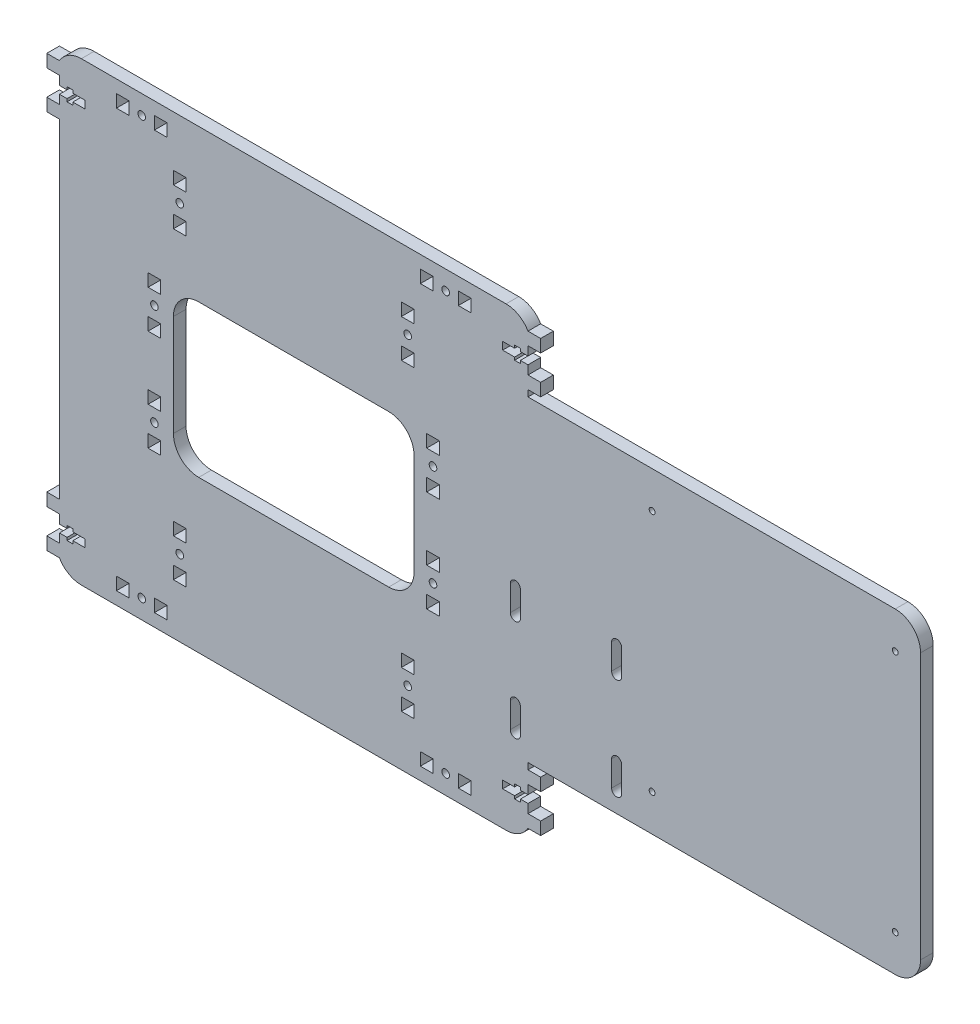
SolidWorks part; units mm, degrees
ref_plane "Front Plane" through (0, 0, 0) normal (0, 0, 1) x (1, 0, 0)
ref_plane "Top Plane" through (0, 0, 0) normal (0, 1, 0) x (1, 0, 0)
ref_plane "Right Plane" through (0, 0, 0) normal (1, 0, 0) x (0, 0, -1)
sketch "Sketch1" plane through (0, 0, 0) normal (0, 0, 1) x (1, 0, 0)
  line L0 (0, 0) -> (264.3375, 0) construction
  line L1 (-92.5, 90) -> (92.5, 90)
  line L2 (-92.5, 90) -> (-92.5, -90) construction
  line L3 (-92.5, -90) -> (92.5, -90)
  line L4 (92.5, 90) -> (92.5, -90) construction
  line L5 (0, 0) -> (0, 175.0626) construction
  line L6 (-92.5, 82.5) -> (92.5, 82.5) construction
  line L7 (92.5, -82.5) -> (-92.5, -82.5) construction
  line L8 (-92.5, 75) -> (-91.2792, 75) construction
  line L9 (-92.5, 76.5) -> (-92.5, 80)
  line L10 (-97.5, 80) -> (-97.5, 85)
  line L11 (-97.5, 85) -> (-92.5, 85)
  line L12 (-97.5, 80) -> (-92.5, 80)
  line L13 (-92.5, 73.5) -> (-92.5, 70)
  line L14 (-92.5, 70) -> (-97.5, 70)
  line L15 (-97.5, 70) -> (-97.5, 65)
  line L16 (-97.5, 65) -> (-92.5, 65)
  line L17 (-92.5, 76.5) -> (-92.5, 73.5) construction
  line L18 (-92.5, 73.5) -> (-89.5, 73.5)
  line L19 (-87.2, 73.5) -> (-87.2, 72.4)
  line L20 (-89.5, 77.6) -> (-87.2, 77.6)
  line L21 (-89.5, 72.4) -> (-89.5, 73.5)
  line L22 (-87.2, 73.5) -> (-82.5, 73.5)
  line L23 (-82.5, 73.5) -> (-82.5, 76.5)
  line L24 (-82.5, 76.5) -> (-87.2, 76.5)
  line L25 (-89.5, 76.5) -> (-89.5, 77.6)
  line L26 (-87.2, 72.4) -> (-89.5, 72.4)
  line L27 (-87.2, 77.6) -> (-87.2, 76.5)
  line L28 (-89.5, 76.5) -> (-92.5, 76.5)
  line L29 (-82.5, 75) -> (-92.5, 75) construction
  line L30 (-97.5, -85) -> (-92.5, -85)
  line L31 (-97.5, -80) -> (-97.5, -85)
  line L32 (-97.5, -80) -> (-92.5, -80)
  line L33 (-92.5, -76.5) -> (-92.5, -80)
  line L34 (-89.5, -76.5) -> (-92.5, -76.5)
  line L35 (-89.5, -76.5) -> (-89.5, -77.6)
  line L36 (-89.5, -77.6) -> (-87.2, -77.6)
  line L37 (-87.2, -77.6) -> (-87.2, -76.5)
  line L38 (-82.5, -76.5) -> (-87.2, -76.5)
  line L39 (-82.5, -73.5) -> (-82.5, -76.5)
  line L40 (-87.2, -73.5) -> (-82.5, -73.5)
  line L41 (-87.2, -73.5) -> (-87.2, -72.4)
  line L42 (-87.2, -72.4) -> (-89.5, -72.4)
  line L43 (-89.5, -72.4) -> (-89.5, -73.5)
  line L44 (-92.5, -73.5) -> (-89.5, -73.5)
  line L45 (-92.5, -73.5) -> (-92.5, -70)
  line L46 (-92.5, -70) -> (-97.5, -70)
  line L47 (-97.5, -70) -> (-97.5, -65)
  line L48 (-97.5, -65) -> (-92.5, -65)
  line L49 (82.5, 75) -> (92.5, 75) construction
  line L50 (92.5, 76.5) -> (92.5, 73.5) construction
  line L51 (92.5, 75) -> (91.2792, 75) construction
  line L52 (97.5, -65) -> (92.5, -65)
  line L53 (97.5, -70) -> (97.5, -65)
  line L54 (92.5, -70) -> (97.5, -70)
  line L55 (92.5, -73.5) -> (92.5, -70)
  line L56 (92.5, -73.5) -> (89.5, -73.5)
  line L57 (89.5, -72.4) -> (89.5, -73.5)
  line L58 (87.2, -72.4) -> (89.5, -72.4)
  line L59 (87.2, -73.5) -> (87.2, -72.4)
  line L60 (87.2, -73.5) -> (82.5, -73.5)
  line L61 (82.5, -73.5) -> (82.5, -76.5)
  line L62 (82.5, -76.5) -> (87.2, -76.5)
  line L63 (87.2, -77.6) -> (87.2, -76.5)
  line L64 (89.5, -77.6) -> (87.2, -77.6)
  line L65 (89.5, -76.5) -> (89.5, -77.6)
  line L66 (89.5, -76.5) -> (92.5, -76.5)
  line L67 (92.5, -76.5) -> (92.5, -80)
  line L68 (97.5, -80) -> (92.5, -80)
  line L69 (97.5, -80) -> (97.5, -85)
  line L70 (97.5, -85) -> (92.5, -85)
  line L71 (89.5, 76.5) -> (92.5, 76.5)
  line L72 (87.2, 77.6) -> (87.2, 76.5)
  line L73 (87.2, 72.4) -> (89.5, 72.4)
  line L74 (89.5, 76.5) -> (89.5, 77.6)
  line L75 (82.5, 76.5) -> (87.2, 76.5)
  line L76 (82.5, 73.5) -> (82.5, 76.5)
  line L77 (87.2, 73.5) -> (82.5, 73.5)
  line L78 (89.5, 72.4) -> (89.5, 73.5)
  line L79 (89.5, 77.6) -> (87.2, 77.6)
  line L80 (87.2, 73.5) -> (87.2, 72.4)
  line L81 (92.5, 73.5) -> (89.5, 73.5)
  line L82 (97.5, 65) -> (92.5, 65)
  line L83 (97.5, 70) -> (97.5, 65)
  line L84 (92.5, 70) -> (97.5, 70)
  line L85 (92.5, 73.5) -> (92.5, 70)
  line L86 (97.5, 80) -> (92.5, 80)
  line L87 (97.5, 85) -> (92.5, 85)
  line L88 (97.5, 80) -> (97.5, 85)
  line L89 (92.5, 76.5) -> (92.5, 80)
  line L90 (92.5, 90) -> (92.5, 85)
  line L91 (92.5, 65) -> (92.5, -65) construction
  line L92 (92.5, -85) -> (92.5, -90)
  line L93 (-92.5, -85) -> (-92.5, -90)
  line L94 (-92.5, 65) -> (-92.5, -65) construction
  line L95 (-92.5, 90) -> (-92.5, 85)
  line L96 (92.5, 65) -> (92.5, 62.5)
  line L97 (-47.5, 30) -> (47.5, 30)
  line L98 (-47.5, 30) -> (-47.5, -30)
  line L99 (-47.5, -30) -> (47.5, -30)
  line L100 (47.5, 30) -> (47.5, -30)
  line L101 (92.5, 62.5) -> (247.5, 62.5)
  line L102 (247.5, 62.5) -> (247.5, -62.5)
  line L103 (247.5, -62.5) -> (92.5, -62.5)
  line L104 (92.5, -62.5) -> (92.5, -65)
  line L105 (127.5, -49.75) -> (73.57, -49.75) construction
  line L106 (127.5, -9.75) -> (73.57, -9.75) construction
  line L107 (127.5, -9.75) -> (127.5, -49.75) construction
  line L108 (127.5, -14.75) -> (127.5, -4.75) construction
  line L109 (125.5, -14.75) -> (125.5, -4.75)
  line L110 (129.5, -14.75) -> (129.5, -4.75)
  line L111 (87.5, -14.75) -> (87.5, -4.75) construction
  line L112 (85.5, -14.75) -> (85.5, -4.75)
  line L113 (89.5, -14.75) -> (89.5, -4.75)
  line L114 (87.5, -54.75) -> (87.5, -44.75) construction
  line L115 (85.5, -54.75) -> (85.5, -44.75)
  line L116 (89.5, -54.75) -> (89.5, -44.75)
  line L117 (127.5, -54.75) -> (127.5, -44.75) construction
  line L118 (125.5, -54.75) -> (125.5, -44.75)
  line L119 (129.5, -54.75) -> (129.5, -44.75)
  line L120 (-92.5, 65) -> (-92.5, -65)
  line L126 (141.5, 48) -> (237.5, 48) construction
  line L127 (141.5, 48) -> (141.5, -48) construction
  line L128 (141.5, -48) -> (237.5, -48) construction
  line L129 (237.5, 48) -> (237.5, -48) construction
  arc A4 (125.5, -14.75) -> (129.5, -14.75) centre (127.5, -14.75) ccw
  arc A5 (129.5, -4.75) -> (125.5, -4.75) centre (127.5, -4.75) ccw
  arc A6 (85.5, -14.75) -> (89.5, -14.75) centre (87.5, -14.75) ccw
  arc A7 (89.5, -4.75) -> (85.5, -4.75) centre (87.5, -4.75) ccw
  arc A8 (85.5, -54.75) -> (89.5, -54.75) centre (87.5, -54.75) ccw
  arc A9 (89.5, -44.75) -> (85.5, -44.75) centre (87.5, -44.75) ccw
  arc A10 (125.5, -54.75) -> (129.5, -54.75) centre (127.5, -54.75) ccw
  arc A11 (129.5, -44.75) -> (125.5, -44.75) centre (127.5, -44.75) ccw
  circle A12 centre (141.5, 48) radius 1.15
  circle A13 centre (237.5, 48) radius 1.15
  circle A14 centre (237.5, -48) radius 1.15
  circle A15 centre (141.5, -48) radius 1.15
  point P113 (127.5, -9.75)
  point P118 (0, 0)
  point P119 (41.7626, 62.5)
  point P122 (87.5, -9.75)
  point P129 (87.5, -49.75)
  point P136 (127.5, -49.75)
  point P141 (0, 0)
  line B0 (-65, 82.5) -> (-55, 82.5) construction
  line B1 (-65, 85) -> (-70, 85)
  line B2 (-65, 85) -> (-65, 80)
  line B3 (-65, 80) -> (-70, 80)
  line B4 (-70, 85) -> (-70, 80)
  line B5 (-55, 85) -> (-50, 85)
  line B6 (-55, 85) -> (-55, 80)
  line B7 (-55, 80) -> (-50, 80)
  line B8 (-50, 85) -> (-50, 80)
  line B9 (-60, 82.5) -> (-60, 89.4724) construction
  circle B10 centre (-60, 82.5) radius 1.5
  line B11 (65, 85) -> (70, 85)
  line B12 (65, 85) -> (65, 80)
  line B13 (65, 80) -> (70, 80)
  line B14 (70, 85) -> (70, 80)
  line B15 (55, 85) -> (50, 85)
  line B16 (55, 85) -> (55, 80)
  line B17 (55, 80) -> (50, 80)
  line B18 (50, 85) -> (50, 80)
  circle B19 centre (60, 82.5) radius 1.5
  line B20 (65, -85) -> (70, -85)
  line B21 (65, -85) -> (65, -80)
  line B22 (65, -80) -> (70, -80)
  line B23 (70, -85) -> (70, -80)
  line B24 (55, -85) -> (50, -85)
  line B25 (55, -85) -> (55, -80)
  line B26 (55, -80) -> (50, -80)
  line B27 (50, -85) -> (50, -80)
  circle B28 centre (60, -82.5) radius 1.5
  line B29 (-65, -85) -> (-70, -85)
  line B30 (-65, -85) -> (-65, -80)
  line B31 (-65, -80) -> (-70, -80)
  line B32 (-70, -85) -> (-70, -80)
  line B33 (-55, -85) -> (-50, -85)
  line B34 (-55, -85) -> (-55, -80)
  line B35 (-55, -80) -> (-50, -80)
  line B36 (-50, -85) -> (-50, -80)
  circle B37 centre (-60, -82.5) radius 1.5
  line B38 (55, 25) -> (55, 15) construction
  line B39 (57.5, 25) -> (57.5, 30)
  line B40 (57.5, 25) -> (52.5, 25)
  line B41 (52.5, 25) -> (52.5, 30)
  line B42 (57.5, 30) -> (52.5, 30)
  line B43 (57.5, 15) -> (57.5, 10)
  line B44 (57.5, 15) -> (52.5, 15)
  line B45 (52.5, 15) -> (52.5, 10)
  line B46 (57.5, 10) -> (52.5, 10)
  line B47 (55, 20) -> (61.9724, 20) construction
  circle B48 centre (55, 20) radius 1.5
  line B49 (-57.5, 25) -> (-57.5, 30)
  line B50 (-57.5, 25) -> (-52.5, 25)
  line B51 (-52.5, 25) -> (-52.5, 30)
  line B52 (-57.5, 30) -> (-52.5, 30)
  line B53 (-57.5, 15) -> (-57.5, 10)
  line B54 (-57.5, 15) -> (-52.5, 15)
  line B55 (-52.5, 15) -> (-52.5, 10)
  line B56 (-57.5, 10) -> (-52.5, 10)
  line B57 (-55, 20) -> (-61.9724, 20) construction
  circle B58 centre (-55, 20) radius 1.5
  line B59 (57.5, -25) -> (57.5, -30)
  line B60 (57.5, -25) -> (52.5, -25)
  line B61 (52.5, -25) -> (52.5, -30)
  line B62 (57.5, -30) -> (52.5, -30)
  line B63 (57.5, -15) -> (57.5, -10)
  line B64 (57.5, -15) -> (52.5, -15)
  line B65 (52.5, -15) -> (52.5, -10)
  line B66 (57.5, -10) -> (52.5, -10)
  circle B67 centre (55, -20) radius 1.5
  line B68 (-57.5, -25) -> (-57.5, -30)
  line B69 (-57.5, -25) -> (-52.5, -25)
  line B70 (-52.5, -25) -> (-52.5, -30)
  line B71 (-57.5, -30) -> (-52.5, -30)
  line B72 (-57.5, -15) -> (-57.5, -10)
  line B73 (-57.5, -15) -> (-52.5, -15)
  line B74 (-52.5, -15) -> (-52.5, -10)
  line B75 (-57.5, -10) -> (-52.5, -10)
  line B76 (-55, -20) -> (-61.9724, -20) construction
  circle B77 centre (-55, -20) radius 1.5
  line B78 (47.5, 65) -> (47.5, 70)
  line B79 (47.5, 65) -> (42.5, 65)
  line B80 (42.5, 65) -> (42.5, 70)
  line B81 (47.5, 70) -> (42.5, 70)
  line B82 (47.5, 55) -> (47.5, 50)
  line B83 (47.5, 55) -> (42.5, 55)
  line B84 (42.5, 55) -> (42.5, 50)
  line B85 (47.5, 50) -> (42.5, 50)
  circle B86 centre (45, 60) radius 1.5
  line B87 (-47.5, 65) -> (-47.5, 70)
  line B88 (-47.5, 65) -> (-42.5, 65)
  line B89 (-42.5, 65) -> (-42.5, 70)
  line B90 (-47.5, 70) -> (-42.5, 70)
  line B91 (-47.5, 55) -> (-47.5, 50)
  line B92 (-47.5, 55) -> (-42.5, 55)
  line B93 (-42.5, 55) -> (-42.5, 50)
  line B94 (-47.5, 50) -> (-42.5, 50)
  circle B95 centre (-45, 60) radius 1.5
  line B96 (47.5, -65) -> (47.5, -70)
  line B97 (47.5, -65) -> (42.5, -65)
  line B98 (42.5, -65) -> (42.5, -70)
  line B99 (47.5, -70) -> (42.5, -70)
  line B100 (47.5, -55) -> (47.5, -50)
  line B101 (47.5, -55) -> (42.5, -55)
  line B102 (42.5, -55) -> (42.5, -50)
  line B103 (47.5, -50) -> (42.5, -50)
  circle B104 centre (45, -60) radius 1.5
  line B105 (-47.5, -65) -> (-47.5, -70)
  line B106 (-47.5, -65) -> (-42.5, -65)
  line B107 (-42.5, -65) -> (-42.5, -70)
  line B108 (-47.5, -70) -> (-42.5, -70)
  line B109 (-47.5, -55) -> (-47.5, -50)
  line B110 (-47.5, -55) -> (-42.5, -55)
  line B111 (-42.5, -55) -> (-42.5, -50)
  line B112 (-47.5, -50) -> (-42.5, -50)
  circle B113 centre (-45, -60) radius 1.5
  dimension "D22" = 35
  dimension "D23" = 2
  dimension "D31" = 2.3
  dimension "D1" = 165
  dimension "D2" = 7.5
  dimension "D3" = 60
  dimension "D4" = 185
  dimension "D5" = 75
  dimension "D6" = 10
  dimension "D7" = 5
  dimension "D8" = 5
  dimension "D9" = 5.2
  dimension "D10" = 3
  dimension "D11" = 2.3
  dimension "D12" = 3
  dimension "D13" = 10
  dimension "D14" = 55
  dimension "D15" = 40
  dimension "D16" = 95
  dimension "D17" = 60
  dimension "D18" = 155
  dimension "D19" = 2.5
  dimension "D20" = 12.75
  dimension "D21" = 40
  dimension "D24" = 10
  dimension "D25" = 2
  dimension "D27" = 40
  dimension "D28" = 96
  dimension "D29" = 96
  dimension "D30" = 10
  dimension "D32" = 45
  dimension "D33" = 60
  dimension "D26" = 2
sketch_block_instance "Trou M3 plots 5mm-1"
sketch_block "Trou M3 plots 5mm" parameters "D2"=3, "D1"=5, "D3"=5, "D4"=10
sketch_block_instance "Trou M3 plots 5mm-3"
sketch_block_instance "Trou M3 plots 5mm-4"
sketch_block_instance "Trou M3 plots 5mm-5"
sketch_block_instance "Trou M3 plots 5mm-7"
sketch_block_instance "Trou M3 plots 5mm-8"
sketch_block_instance "Trou M3 plots 5mm-9"
sketch_block_instance "Trou M3 plots 5mm-10"
sketch_block_instance "Trou M3 plots 5mm-11"
sketch_block_instance "Trou M3 plots 5mm-12"
sketch_block_instance "Trou M3 plots 5mm-13"
sketch_block_instance "Trou M3 plots 5mm-14"
extrude "Boss-Extrude1" add sketch "Sketch1" along normal blind 5
fillet "Fillet1" radius 10 10 edges at (-92.5, 90, 2.5) (-92.5, -90, 2.5) (92.5, -90, 2.5) (92.5, 90, 2.5) (47.5, -30, 2.5) (-47.5, -30, 2.5) (-47.5, 30, 2.5) (47.5, 30, 2.5) (247.5, -62.5, 2.5) (247.5, 62.5, 2.5)
